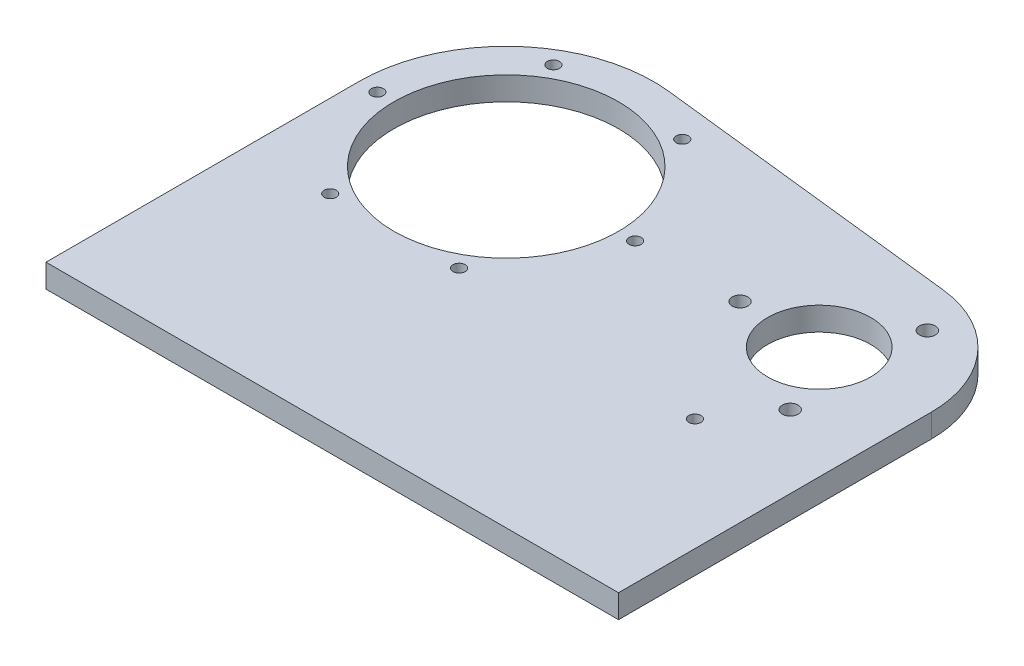
SolidWorks part; units mm, degrees
ref_plane "Front Plane" through (0, 0, 0) normal (0, 0, 1) x (1, 0, 0)
ref_plane "Top Plane" through (0, 0, 0) normal (0, 1, 0) x (1, 0, 0)
ref_plane "Right Plane" through (0, 0, 0) normal (1, 0, 0) x (0, 0, -1)
sketch "Sketch1" plane through (0, 0, 0) normal (0, 1, 0) x (1, 0, 0)
  line L0 (4.4706, 39.7494) -> (88.4088, 30.3089)
  line L1 (-40, 40) -> (115.5, 40)
  line L2 (-40, 40) -> (-40, -85)
  line L3 (-40, -85) -> (115.5, -85)
  line L4 (115.5, 40) -> (115.5, -85)
  line L5 (-40, 40) -> (115.5, -85) construction
  line L6 (-40, -85) -> (115.5, 40) construction
  circle A0 centre (0, 0) radius 40
  circle A1 centre (0, 0) radius 30.5
  circle A2 centre (85, 0) radius 14
  circle A3 centre (85, 0) radius 30.5
  point P4 (37.75, -22.5)
  dimension "D3" = 80
  dimension "D4" = 61
  dimension "D5" = 61
  dimension "D6" = 28
  dimension "D1" = 85
  dimension "D7" = 85
extrude "Boss-Extrude1" add sketch "Sketch1" along normal mid plane 6.35 contours L4 A3 L1 A0 L2 L3 | A0 A1 | A3 A2 region at (41.2029, 0, 46.4583) region at (28.9795, 0, -25.9029) region at (107.0969, 0, -19.751)
hole_wizard "M4x0.7 Tapped Hole1" positions "Sketch4" profile "Sketch5" tap size "M4x0.7" standard "ANSI Metric" end condition up to next
sketch "Sketch4" plane through (0, 3.175, 0) normal (0, 1, 0) x (1, 0, 0)
  line L0 (0, 0) -> (35, 0)
  line L1 (0, 0) -> (17.5, -30.3109)
  line L2 (0, 0) -> (-17.5, -30.3109)
  line L3 (0, 0) -> (-35, 0)
  line L4 (0, 0) -> (-17.5, 30.3109)
  line L5 (0, 0) -> (17.5, 30.3109)
  circle A1 centre (85, -33.75) radius 2.15
  point P5 (35, 0)
  point P16 (17.5, -30.3109)
  point P17 (-17.5, -30.3109)
  point P18 (-35, 0)
  point P19 (-17.5, 30.3109)
  point P20 (17.5, 30.3109)
  point P59 (85, -33.75)
  dimension "D1" = 35
  dimension "D2" = 6
sketch "Sketch5" plane through (85, 3.175, 33.75) normal (1, 0, 0) x (0, 0, 1)
  line L0 (0, 0) -> (0, 6.35)
  line L1 (0, 6.35) -> (1.65, 6.35)
  line L2 (1.65, 6.35) -> (1.65, 0)
  line L5 (1.65, 0) -> (0, 0)
  line L11 (0, -6.35) -> (0, 107.95) construction
  dimension "Thru Tap Drill Dia." = 3.3
  dimension "Thru Tap Drill Depth" = 6.35
cosmetic thread "Hole Thread1" parameters "D2"=4
cosmetic thread "Hole Thread2" parameters "D2"=4
cosmetic thread "Hole Thread3" parameters "D2"=4
cosmetic thread "Hole Thread4" parameters "D2"=4
cosmetic thread "Hole Thread5" parameters "D2"=4
cosmetic thread "Hole Thread6" parameters "D2"=4
cosmetic thread "Hole Thread12" parameters "D2"=4
hole_wizard "M4 Clearance Hole1" positions "Sketch6" profile "Sketch7" hole size "M4" standard "ANSI Metric" end condition up to next
sketch "Sketch6" plane through (0, 3.175, 0) normal (0, 1, 0) x (1, 0, 0)
  line L0 (85, 0) -> (95.75, 18.6195)
  line L1 (85, 0) -> (95.75, -18.6195)
  line L2 (85, 0) -> (63.5, 0)
  point P2 (95.75, 18.6195)
  point P10 (95.75, -18.6195)
  point P11 (63.5, 0)
  point P26 (0, 0)
  point P27 (0, 0)
  point P28 (98.8834, 16.4165)
  dimension "D1" = 21.5
  dimension "D2" = 3
sketch "Sketch7" plane through (63.5, 3.175, 0) normal (1, 0, 0) x (0, 0, 1)
  line L0 (0, 0) -> (0, 6.35)
  line L1 (0, 6.35) -> (2.15, 6.35)
  line L2 (2.15, 6.35) -> (2.15, 0)
  line L5 (2.15, 0) -> (0, 0)
  line L11 (0, -6.35) -> (0, 107.95) construction
  dimension "Thru Hole Dia." = 4.3
  dimension "Thru Hole Depth" = 6.35
